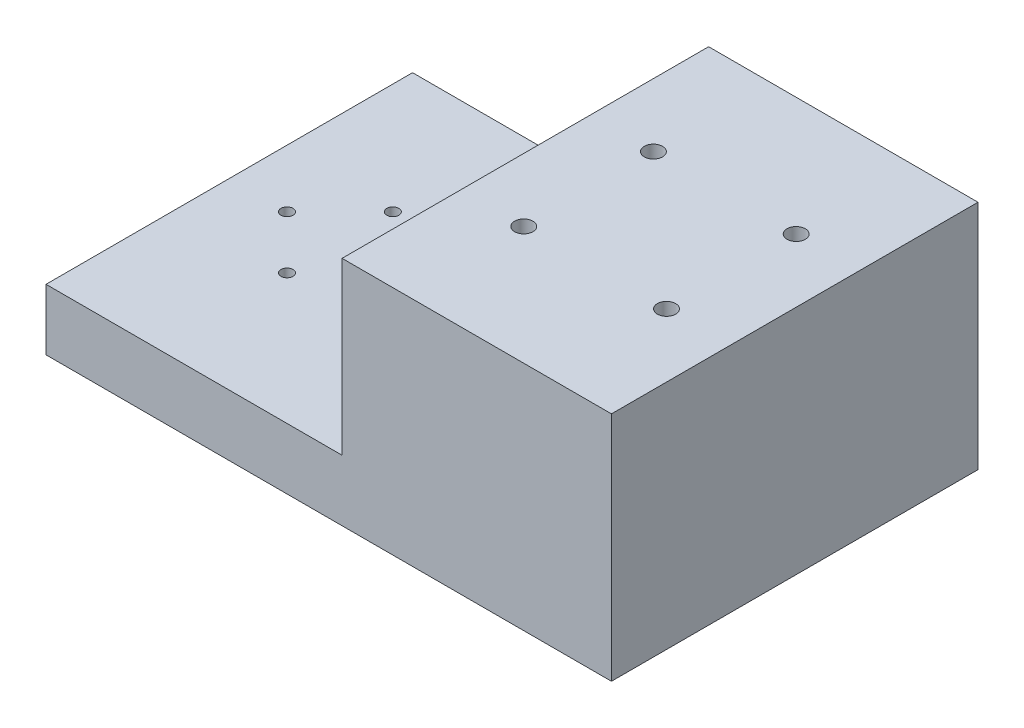
SolidWorks part; units mm, degrees
material "1060 Alloy"
ref_plane "Front Plane" through (0, 0, 0) normal (0, 0, 1) x (1, 0, 0)
ref_plane "Top Plane" through (0, 0, 0) normal (0, 1, 0) x (1, 0, 0)
ref_plane "Right Plane" through (0, 0, 0) normal (1, 0, 0) x (0, 0, -1)
sketch "Sketch1" plane through (0, 0, 0) normal (1, 0, 0) x (0, 0, -1)
  line L0 (0, 0) -> (0, 35.8006) construction
  line L1 (-38.1, 0.5539) -> (38.1, 0.5539)
  line L2 (-38.1, 0.5539) -> (-38.1, 13.2539)
  line L3 (-38.1, 13.2539) -> (38.1, 13.2539)
  line L4 (38.1, 0.5539) -> (38.1, 13.2539)
  point P4 (0, 13.2539)
  dimension "D1" = 12.7
  dimension "D2" = 76.2
extrude "Boss-Extrude1" add sketch "Sketch1" along normal blind 117.55
hole_wizard "Ø2.5mm Dowel Hole2" positions "Sketch7" profile "Sketch6" hole size "Ø2.5" standard "ANSI Metric" end condition through all
sketch "Sketch7" plane through (0, 13.2539, 0) normal (0, 1, 0) x (1, 0, 0)
  line L1 (12, 0) -> (34, 0) construction
  line L3 (0, 38.1) -> (0, -38.1) construction
  point P0 (12, 0)
  point P2 (34, 0)
  point P4 (23, -11)
  point P6 (23, 11)
  dimension "D2" = 22
  dimension "D3" = 22
  dimension "D4" = 11
  dimension "D5" = 11
  dimension "D6" = 11
  dimension "D7" = 12
sketch "Sketch6" plane through (12, 13.2539, 0) normal (1, 0, 0) x (0, 0, 1)
  line L0 (0, 0) -> (0, 12.7)
  line L1 (0, 12.7) -> (1.25, 12.7)
  line L2 (1.25, 12.7) -> (1.25, 0)
  line L5 (1.25, 0) -> (0, 0)
  line L11 (0, -6.35) -> (0, 107.95) construction
  dimension "Thru Hole Dia." = 2.5
  dimension "Thru Hole Depth" = 12.7
sketch "Sketch13" plane through (0, 13.2539, 0) normal (0, 1, 0) x (1, 0, 0)
  line L0 (117.55, 38.1) -> (0, 38.1) construction
  line L1 (117.55, -38.1) -> (61.55, -38.1)
  line L2 (117.55, -38.1) -> (117.55, 38.1)
  line L3 (117.55, 38.1) -> (61.55, 38.1)
  line L4 (61.55, -38.1) -> (61.55, 38.1)
  dimension "D1" = 56
extrude "Boss-Extrude3" add sketch "Sketch13" along normal blind 35.45
sketch "Sketch11" plane through (0, 0.5539, 0) normal (0, 1, 0) x (1, 0, 0)
  line L0 (117.55, 38.1) -> (117.55, -38.1) construction
  line L2 (117.55, -38.1) -> (117.55, 38.1) construction
  circle A2 centre (104.375, 13.4747) radius 3.75
  circle A3 centre (74.695, 13.4747) radius 3.75
  point P0 (117.55, 0)
  dimension "D1" = 13.4747
  dimension "D3" = 7.5
  dimension "D4" = 7.5
  dimension "D6" = 13.175
  dimension "D7" = 29.68
extrude "Cut-Extrude3" cut sketch "Sketch11" along normal blind 24.5
sketch "Sketch14" plane through (0, 25.0539, 0) normal (0, -1, 0) x (1, 0, 0)
  circle A0 centre (104.375, -13.4747) radius 1.905
  circle A1 centre (74.695, -13.4747) radius 1.905
  dimension "D1" = 3.81
  dimension "D2" = 3.81
extrude "Cut-Extrude4" cut sketch "Sketch14" against normal through all
mirror "Mirror2" about plane through (0, 0, 0) normal (0, 0, 1) of "Cut-Extrude4", "Cut-Extrude3"
hole_wizard "Tap Drill for M2.5x0.45 Tap1" positions "Sketch17" profile "Sketch16" hole size "M2.5x0.45" standard "ANSI Metric"
sketch "Sketch17" plane through (0, 0, 0) normal (-1, 0, 0) x (0, 0, 1)
  line L0 (38.1, 13.2539) -> (38.1, 0.5539) construction
  line L1 (-38.1, 0.5539) -> (-38.1, 13.2539) construction
  line L2 (38.1, 0.5539) -> (-38.1, 0.5539) construction
  point P0 (-12.7, 6.9039)
  point P2 (12.7, 6.9039)
  point P6 (38.1, 6.9039)
  dimension "D1" = 25.4
  dimension "D2" = 25.4
  dimension "D3" = 6.35
  dimension "D4" = 6.35
sketch "Sketch16" plane through (0, 6.9039, -12.7) normal (0, 1, 0) x (0, 0, 1)
  line L0 (0, 0) -> (0, 8.9159)
  line L1 (0, 8.9159) -> (1.025, 8.3)
  line L2 (1.025, 8.3) -> (1.025, 0)
  line L5 (1.025, 0) -> (0, 0)
  line L10 (0, 8.9159) -> (-1.025, 8.3) construction
  line L11 (0, -6.35) -> (0, 107.95) construction
  dimension "Hole Dia." = 2.05
  dimension "Hole Depth" = 8.3
  dimension "Drill Angle" = 118
